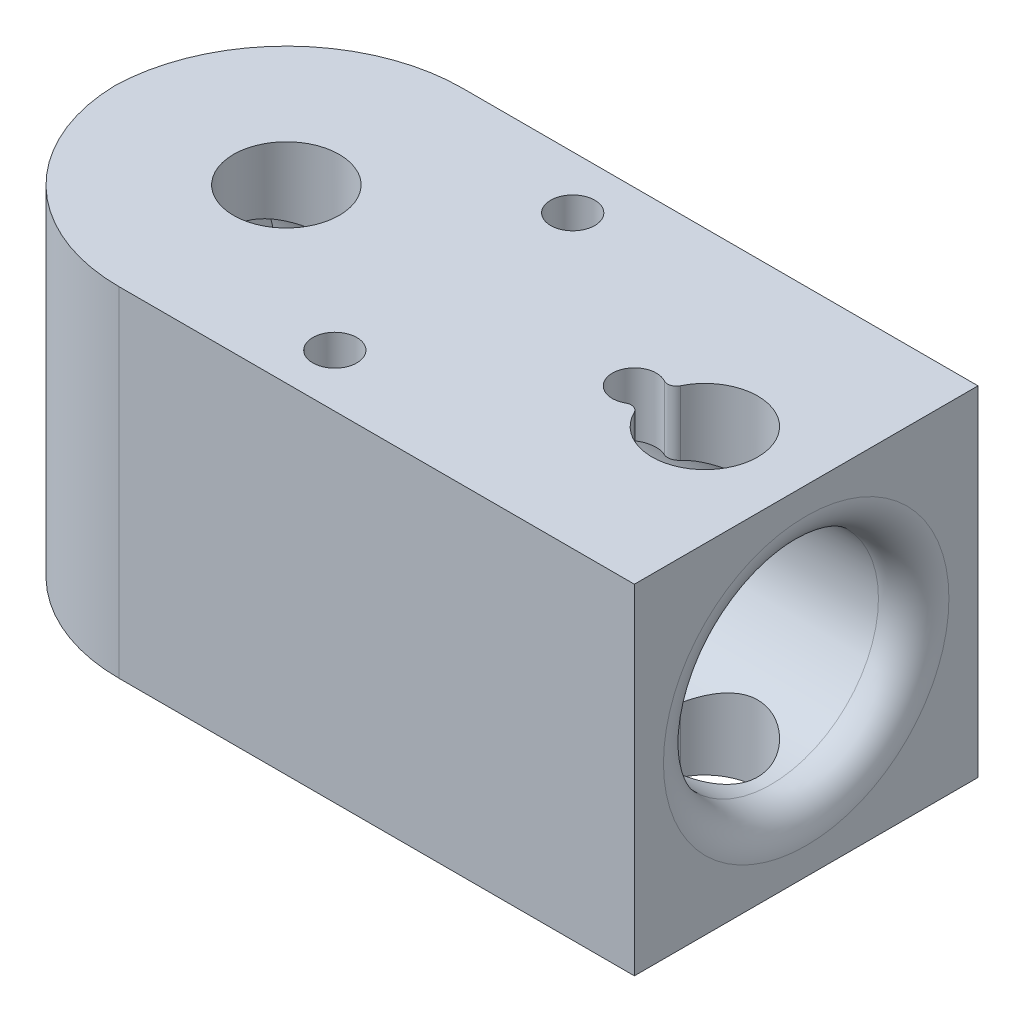
SolidWorks part; units mm, degrees
ref_plane "Front Plane" through (0, 0, 0) normal (0, 0, 1) x (1, 0, 0)
ref_plane "Top Plane" through (0, 0, 0) normal (0, 1, 0) x (1, 0, 0)
ref_plane "Right Plane" through (0, 0, 0) normal (1, 0, 0) x (0, 0, -1)
sketch "Sketch1" plane through (0, 0, 0) normal (0, 1, 0) x (1, 0, 0)
  line L0 (0, -9.75) -> (9.75, -9.75)
  line L1 (0, 0) -> (39.25, 0)
  line L2 (0, 0) -> (0, -19.5)
  line L3 (0, -19.5) -> (39.25, -19.5)
  line L4 (39.25, 0) -> (39.25, -19.5)
  line L5 (19.25, -16.5) -> (19.25, -19.5)
  line L6 (39.25, -16.5) -> (19.25, -16.5)
  line L7 (33.5, -9.75) -> (29.5, -9.75)
  line L8 (39.25, -3) -> (19.25, -3)
  line L9 (39.25, -9.75) -> (33.5, -9.75)
  line L10 (19.25, -3) -> (19.25, 0)
  circle A0 centre (19.25, -16.5) radius 1.25
  circle A1 centre (19.25, -3) radius 1.25
  circle A2 centre (9.75, -9.75) radius 3
  circle A3 centre (33.5, -9.75) radius 3
  circle A4 centre (29.5, -9.75) radius 1.25
  dimension "D4" = 5.75
  dimension "D8" = 2.5
  dimension "D10" = 2.5
  dimension "D11" = 6
  dimension "D12" = 6
  dimension "D14" = 2.5
  dimension "D1" = 39.25
  dimension "D2" = 19.5
  dimension "D3" = 9.75
  dimension "D5" = 20
  dimension "D6" = 20
  dimension "D7" = 3
  dimension "D9" = 3
  dimension "D13" = 4
extrude "Boss-Extrude1" add sketch "Sketch1" along normal blind 19.25 contours A3 L4 L8 A1 L10 L1 L2 A2 L3 L5 A0 L6 | A1 L8 L4 L1 L10 | A0 L5 L3 L4 L6 region at (17.3535, 0, 9.75) region at (29.4477, 0, 1.4798) region at (29.4477, 0, 18.0202)
sketch "Sketch2" plane through (39.25, 0, 0) normal (1, 0, 0) x (0, 0, -1)
  line L0 (-19.5, 19.25) -> (0, 0)
  circle A0 centre (-9.75, 9.625) radius 6.1
  dimension "D1" = 12.2
extrude "Cut-Extrude1" cut sketch "Sketch2" against normal blind 36.25 contours L0 A0 | L0 A0 region at (39.25, 11.4674, 7.9312) region at (39.25, 7.7826, 11.5688)
fillet "Fillet1" radius 2 1 edges at (39.25, 9.625, 3.65)
fillet "Fillet3" radius 10 2 edges at (0, 9.625, 19.5) (0, 9.625, 0)
sketch "Sketch4" plane through (3, 0, 0) normal (1, 0, 0) x (0, 0, -1)
  circle A0 centre (-9.75, 9.625) radius 5
extrude "Cut-Extrude3" cut sketch "Sketch4" against normal up to next
fillet "Fillet4" radius 0.5 4 edges at (30.5703, 1.7796, 10.3957) (30.5703, 1.7796, 9.1043) (30.5703, 17.4704, 10.3957) (30.5703, 17.4704, 9.1043)
